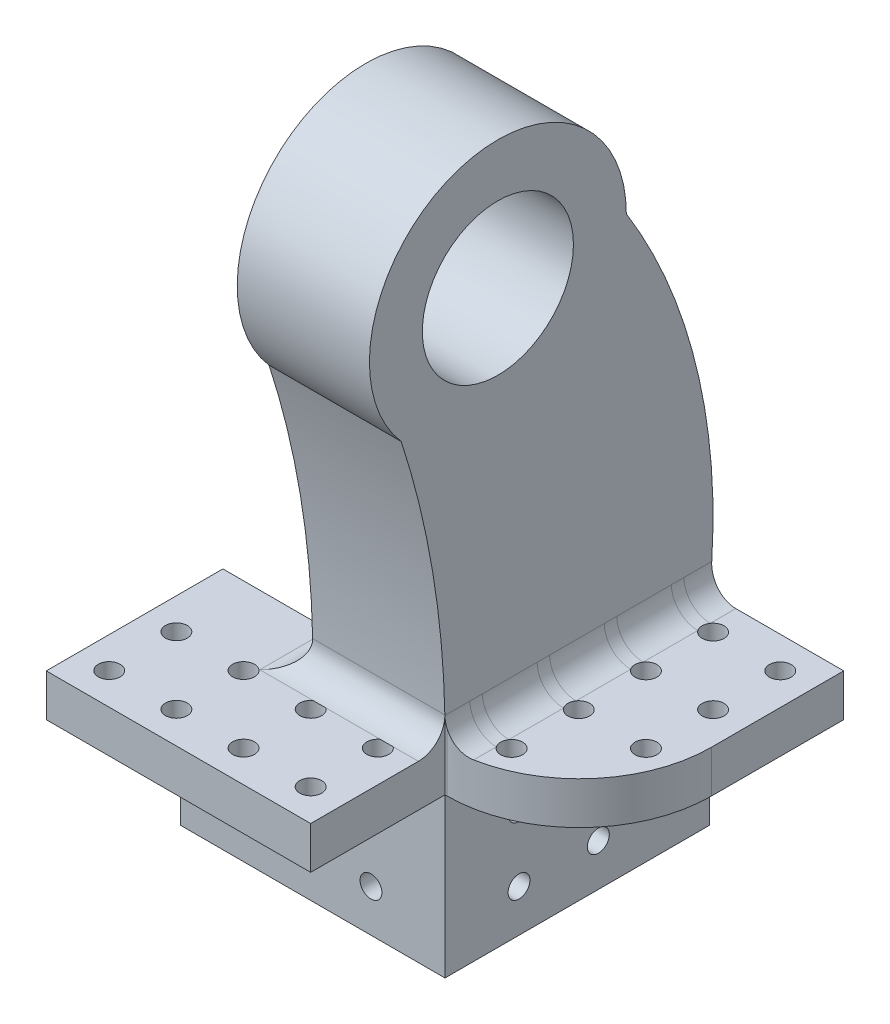
SolidWorks part; units mm, degrees
ref_plane "Alzado" through (0, 0, 0) normal (0, 0, 1) x (1, 0, 0)
ref_plane "Planta" through (0, 0, 0) normal (0, 1, 0) x (1, 0, 0)
ref_plane "Vista lateral" through (0, 0, 0) normal (1, 0, 0) x (0, 0, -1)
sketch "Croquis1" plane through (0, 0, 0) normal (0, 1, 0) x (1, 0, 0)
  line L1 (0, 0) -> (25.4, 0)
  line L3 (0, 50) -> (25.4, 50)
  line L4 (25.4, 0) -> (25.4, 50)
  line L6 (0, 0) -> (0, -25.4)
  line L7 (0, -25.4) -> (-50, -25.4)
  line L8 (-50, 0) -> (-50, -25.4)
  line L10 (-50, 0) -> (-50, 50)
  line L11 (-50, 50) -> (0, 50)
  dimension "D1" = 25.4
  dimension "D2" = 50
  dimension "D3" = 50
  dimension "D4" = 25.4
extrude "Saliente-Extruir1" add sketch "Croquis1" along normal blind 8
fillet "Redondeo1" radius 25 1 edges at (25.4, 4, 0)
sketch "Croquis2" plane through (0, 0, 0) normal (0, -1, 0) x (1, 0, 0)
  line L0 (-50, -50) -> (-50, 25.4) construction
  line L1 (0, 0) -> (-50, 0)
  line L2 (0, 0) -> (0, -8)
  line L3 (-8, -8) -> (-50, -8)
  line L4 (-50, 0) -> (-50, -8)
  line L5 (25.4, -50) -> (-50, -50) construction
  line L6 (0, -50) -> (-8, -50)
  line L7 (0, -50) -> (0, -8)
  line L9 (-8, -50) -> (-8, -8)
  dimension "D1" = 8
  dimension "D2" = 8
extrude "Saliente-Extruir2" add sketch "Croquis2" along normal blind 30
sketch "Croquis3" plane through (0, 0, 0) normal (1, 0, 0) x (0, 0, -1)
  line L0 (25, 8) -> (0, 8) construction
  line L1 (50, 8) -> (50, 0) construction
  line L2 (0, 8) -> (50, 8)
  circle A0 centre (10, 78) radius 14.29
  arc A1 (34.29, 78) -> (-8.2758, 62) centre (10, 78) ccw
  arc A2 (50, 8) -> (34.29, 78) centre (-59.3181, 20.2288) ccw
  arc A3 (0, 8) -> (-8.2758, 62) centre (-169.9926, 9.5819) ccw
  dimension "D1" = 28.58
  dimension "D2" = 10
  dimension "D5" = 110
  dimension "D6" = 170
  dimension "D3" = 70
  dimension "D4" = 40
  dimension "D7" = 54
extrude "Saliente-Extruir3" add sketch "Croquis3" against normal blind 25
sketch "Croquis4" plane through (0, 8, 0) normal (0, 1, 0) x (1, 0, 0)
  line L0 (-25, 0) -> (-25, 50) construction
  line L1 (-50, 50) -> (-25, 50)
  line L2 (-50, 50) -> (-50, 8)
  line L3 (-50, 8) -> (-25, 8)
  line L4 (-25, 50) -> (-25, 8)
  dimension "D1" = 42
extrude "Cortar-Extruir1" cut sketch "Croquis4" against normal through all
fillet "Redondeo3" radius 5 1 edges at (-12.5, 8, 0)
sketch "Croquis5" plane through (0, 8, 0) normal (0, 1, 0) x (1, 0, 0)
  line L0 (0, -25.4) -> (0, -5.028) construction
  line L1 (-50, -25.4) -> (0, -25.4) construction
  line L2 (25.4, 25) -> (25.4, 50) construction
  line L3 (25.4, 50) -> (0, 50) construction
  circle A0 centre (-6, -19.4) radius 2.07
  circle A1 centre (-18.7, -19.4) radius 2.07
  circle A2 centre (-31.4, -19.4) radius 2.07
  circle A3 centre (-44.1, -19.4) radius 2.07
  circle A4 centre (-6, -6.7) radius 2.07
  circle A5 centre (-44.1, -6.7) radius 2.07
  circle A6 centre (-31.4, -6.7) radius 2.07
  circle A7 centre (-18.7, -6.7) radius 2.07
  circle A8 centre (19.4, 44) radius 2.07
  circle A9 centre (19.4, 31.3) radius 2.07
  circle A10 centre (19.4, 18.6) radius 2.07
  circle A12 centre (6.7, 44) radius 2.07
  circle A13 centre (6.7, 5.9) radius 2.07
  circle A14 centre (6.7, 18.6) radius 2.07
  circle A15 centre (6.7, 31.3) radius 2.07
  circle A16 centre (19.4, 5.9) radius 2.07 [skipped]
  dimension "D1" = 4.14
  dimension "D2" = 6
  dimension "D3" = 6
  dimension "D6" = 4.14
  dimension "D7" = 6
  dimension "D8" = 6
  dimension "D4" = 4
  dimension "D5" = 2
  dimension "D9" = 4
  dimension "D10" = 2
extrude "Cortar-Extruir2" cut sketch "Croquis5" against normal through all
fillet "Redondeo2" radius 5 6 edges at (-16.5, 0, -8) (0, 8, -25) (-25, 8, -1.486) (-25, 4, -8) (-25, 0, -29) (-16.5, 0, -50)
sketch "Croquis6" plane through (0, 0, -8) normal (0, 0, -1) x (-1, 0, 0)
  line L0 (50, -30) -> (8, -30) construction
  line L1 (50, -30) -> (50, 8) construction
  circle A0 centre (44, -22) radius 2.07
  circle A1 centre (29, -22) radius 2.07
  circle A2 centre (14, -22) radius 2.07
  circle A6 centre (14, -10) radius 2.07
  circle A7 centre (29, -10) radius 2.07
  circle A8 centre (44, -10) radius 2.07
  dimension "D1" = 4.14
  dimension "D2" = 8
  dimension "D3" = 6
  dimension "D4" = 3
  dimension "D5" = 2
extrude "Cortar-Extruir3" cut sketch "Croquis6" against normal through all
sketch "Croquis7" plane through (-8, 0, 0) normal (-1, 0, 0) x (0, 0, 1)
  line L0 (-8, -30) -> (-50, -30) construction
  line L1 (-50, -30) -> (-50, 5) construction
  circle A0 centre (-44, -22) radius 2.07
  circle A3 centre (-29, -22) radius 2.07
  circle A4 centre (-14, -22) radius 2.07
  circle A5 centre (-44, -9.3) radius 2.07
  circle A6 centre (-29, -9.3) radius 2.07
  circle A7 centre (-14, -9.3) radius 2.07
  dimension "D1" = 4.14
  dimension "D2" = 8
  dimension "D3" = 6
  dimension "D4" = 3
  dimension "D5" = 2
extrude "Cortar-Extruir4" cut sketch "Croquis7" against normal through all
